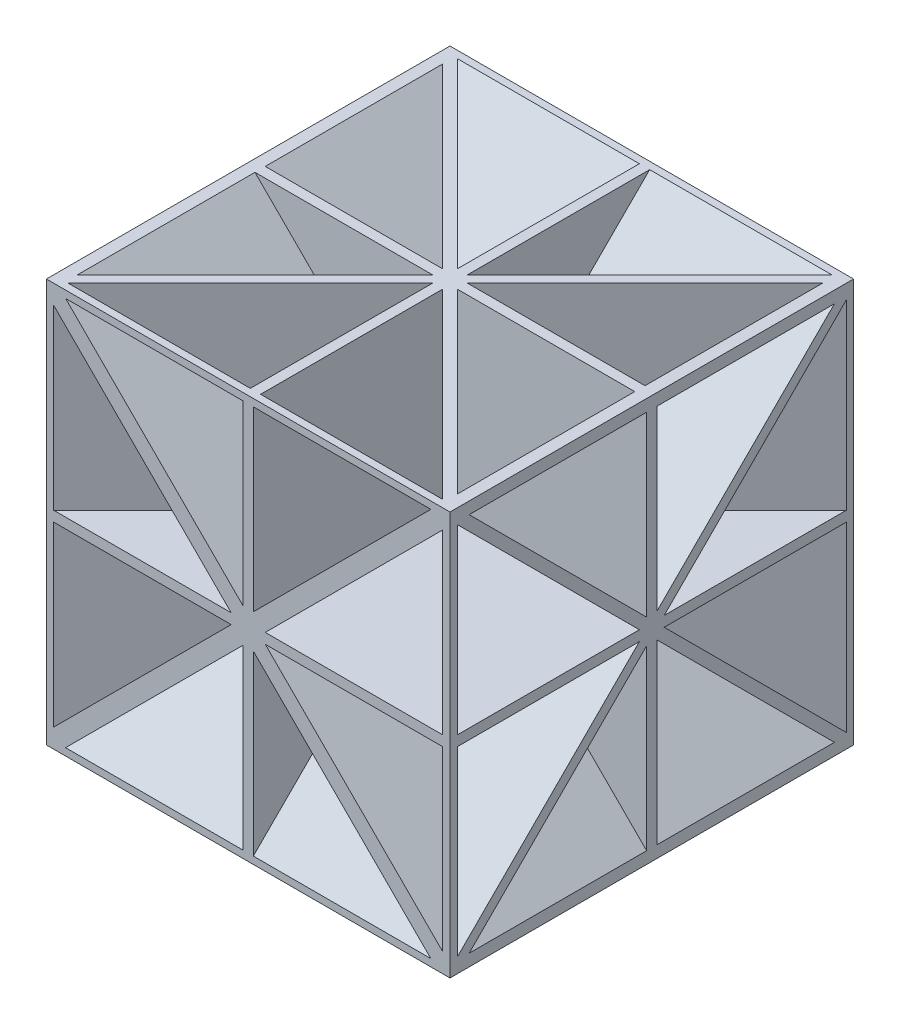
SolidWorks part; units mm, degrees
note: '?' marks a value the reader was unsure of.
ref_plane "Front Plane" through (0, 0, 0) normal (0, 0, 1) x (1, 0, 0)
ref_plane "Top Plane" through (0, 0, 0) normal (0, 1, 0) x (1, 0, 0)
ref_plane "Right Plane" through (0, 0, 0) normal (1, 0, 0) x (0, 0, -1)
sketch "Sketch2" plane through (0, 0, 0) normal (0, 0, 1) x (1, 0, 0)
  line L1 (12.5, -12.5) -> (-12.5, -12.5)
  line L2 (12.5, -12.5) -> (12.5, 12.5)
  line L3 (12.5, 12.5) -> (-12.5, 12.5)
  line L4 (-12.5, -12.5) -> (-12.5, 12.5)
  line L5 (12.5, -12.5) -> (-12.5, 12.5) construction
  line L6 (12.5, 12.5) -> (-12.5, -12.5) construction
  point P0 (0, 0)
  dimension "D1" = 25
  dimension "D2" = 25
sketch "Sketch3" plane through (0, 0, 0) normal (0, 1, 0) x (1, 0, 0)
  line L1 (12.5, -12.5) -> (-12.5, -12.5)
  line L2 (12.5, -12.5) -> (12.5, 12.5)
  line L3 (12.5, 12.5) -> (-12.5, 12.5)
  line L4 (-12.5, -12.5) -> (-12.5, 12.5)
  line L5 (12.5, -12.5) -> (-12.5, 12.5) construction
  line L6 (12.5, 12.5) -> (-12.5, -12.5) construction
  point P0 (0, 0)
  dimension "D1" = 25
  dimension "D2" = 25
sketch "Sketch4" plane through (0, 0, 0) normal (1, 0, 0) x (0, 0, -1)
  line L1 (12.5, -12.5) -> (-12.5, -12.5)
  line L2 (12.5, -12.5) -> (12.5, 12.5)
  line L3 (12.5, 12.5) -> (-12.5, 12.5)
  line L4 (-12.5, -12.5) -> (-12.5, 12.5)
  line L5 (12.5, -12.5) -> (-12.5, 12.5) construction
  line L6 (12.5, 12.5) -> (-12.5, -12.5) construction
  point P0 (0, 0)
  dimension "D1" = 25
  dimension "D2" = 25
extrude "Boss-Extrude1" add sketch "Sketch2" along normal mid plane 0.61
extrude "Boss-Extrude2" add sketch "Sketch3" along normal mid plane 0.61
extrude "Boss-Extrude3" add sketch "Sketch4" along normal mid plane 0.61
ref_plane "Plane1" through (0, 12.5, 0) normal (0, 1, 0) x (1, 0, 0)
ref_plane "Plane2" through (0, -12.5, 0) normal (0, 1, 0) x (1, 0, 0)
ref_plane "Plane3" through (12.5, 0, 0) normal (1, 0, 0) x (0, 0, -1)
ref_plane "Plane4" through (-12.5, 0, 0) normal (1, 0, 0) x (0, 0, -1)
sketch "Sketch8" plane through (0, -12.5, 0) normal (0, 1, 0) x (1, 0, 0)
  line L0 (-12.5, -13.75) -> (-12.5, 13.75) construction
  line L1 (12.5, -12.5) -> (-12.5, -12.5)
  line L2 (12.5, -12.5) -> (12.5, 12.5)
  line L3 (12.5, 12.5) -> (-12.5, 12.5)
  line L4 (-12.5, -12.5) -> (-12.5, 12.5)
  line L5 (12.5, -12.5) -> (-12.5, 12.5) construction
  line L6 (12.5, 12.5) -> (-12.5, -12.5) construction
  point P0 (0, 0)
  dimension "D1" = 25
sketch "Sketch9" plane through (0, 12.5, 0) normal (0, 1, 0) x (1, 0, 0)
  line L1 (12.5, -12.5) -> (-12.5, -12.5)
  line L2 (12.5, -12.5) -> (12.5, 12.5)
  line L3 (12.5, 12.5) -> (-12.5, 12.5)
  line L4 (-12.5, -12.5) -> (-12.5, 12.5)
  line L5 (12.5, -12.5) -> (-12.5, 12.5) construction
  line L6 (12.5, 12.5) -> (-12.5, -12.5) construction
  point P0 (0, 0)
  dimension "D1" = 25
  dimension "D2" = 25
sketch3d "3DSketch1"
  line L4 (12.5, 12.5, -12.5) -> (12.5, -12.5, -12.5)
  line L5 (12.5, -12.5, -12.5) -> (-12.5, -12.5, 12.5)
  line L6 (-12.5, -12.5, 12.5) -> (-12.5, 12.5, 12.5)
  line L7 (-12.5, 12.5, 12.5) -> (12.5, 12.5, -12.5)
extrude "Boss-Extrude4" add sketch "3DSketch1" along direction (-0.7071, 0, -0.7071) on the side of the normal mid plane 0.61
ref_axis "Axis1" through (0, 0, -14.139) along (0, 0, 1)?
pattern_circular "CirPattern1" count 4 over 360 about axis through (0, 0, 0) along (0, 0, 1) of "Boss-Extrude4"
ref_axis "Axis2" through (-14.139, 0, 0) along (1, 0, 0)?
sketch3d "3DSketch2"
  line L0 (12.5, -12.5, -12.5) -> (-12.5, 12.5, -12.5)
  line L1 (-12.5, 12.5, -12.5) -> (-12.5, 12.5, 12.5)
  line L2 (-12.5, 12.5, 12.5) -> (12.5, -12.5, 12.5)
  line L3 (12.5, -12.5, 12.5) -> (12.5, -12.5, -12.5)
  line L4 (12.5, 12.5, -12.5) -> (-12.5, -12.5, -12.5) construction
extrude "Boss-Extrude5" add sketch "3DSketch2" along direction (-0.7071, -0.7071, 0) on the side of the normal mid plane 1 separate body
pattern_circular "CirPattern3" count 4 over 360 about axis through (0, 0, 0) along (0, 0, 1) of "Boss-Extrude5"
combine bodies "Combine1" bodies to combine 105 107
sketch "Sketch10" plane through (0, 0, 12.5) normal (0, 0, 1) x (1, 0, 0)
  line L5 (12, -12) -> (-12, -12)
  line L6 (0, 16.6777) -> (0, -16.6777) construction
  line L7 (16.1012, -15.1405) -> (-16.1012, -15.1405)
  line L8 (16.1012, -15.1405) -> (16.1012, 15.1405)
  line L9 (16.1012, 15.1405) -> (-16.1012, 15.1405)
  line L10 (-16.1012, -15.1405) -> (-16.1012, 15.1405)
  line L11 (16.1012, -15.1405) -> (-16.1012, 15.1405) construction
  line L12 (16.1012, 15.1405) -> (-16.1012, -15.1405) construction
  line L13 (12, -12) -> (12, 12)
  line L14 (12, 12) -> (-12, 12)
  line L15 (-12, -12) -> (-12, 12)
  line L16 (12, -12) -> (-12, 12) construction
  line L17 (12, 12) -> (-12, -12) construction
  point P0 (0, 0)
  point P1 (0, 0)
  point P7 (0, 0)
  dimension "D1" = 12
  dimension "D2" = 12
  dimension "D3" = 12
  dimension "D4" = 12
extrude "Cut-Extrude1" cut sketch "Sketch10" against normal through all both and the other way through all
sketch "Sketch11" plane through (12, 0, 0) normal (1, 0, 0) x (0, 0, -1)
  line L6 (14.4401, -13.3293) -> (-14.4401, -13.3293)
  line L7 (14.4401, -13.3293) -> (14.4401, 13.3293)
  line L12 (14.4401, 13.3293) -> (-14.4401, 13.3293)
  line L13 (-14.4401, -13.3293) -> (-14.4401, 13.3293)
  line L14 (14.4401, -13.3293) -> (-14.4401, 13.3293) construction
  line L15 (14.4401, 13.3293) -> (-14.4401, -13.3293) construction
  line L16 (12, -12) -> (-12, -12)
  line L17 (12, -12) -> (12, 12)
  line L18 (12, 12) -> (-12, 12)
  line L19 (-12, -12) -> (-12, 12)
  line L20 (12, -12) -> (-12, 12) construction
  line L21 (12, 12) -> (-12, -12) construction
  point P0 (0, 0)
  point P6 (0, 0)
  dimension "D1" = 12
  dimension "D2" = 12
extrude "Cut-Extrude2" cut sketch "Sketch11" against normal blind 37
equation "\"t\"= 0.61mm"
equation "\"D1@Boss-Extrude1\"=\"t\""
equation "\"D1@Boss-Extrude2\"=\"t\""
equation "\"D1@Boss-Extrude3\"=\"t\""
equation "\"D1@Boss-Extrude4\"=\"t\""
